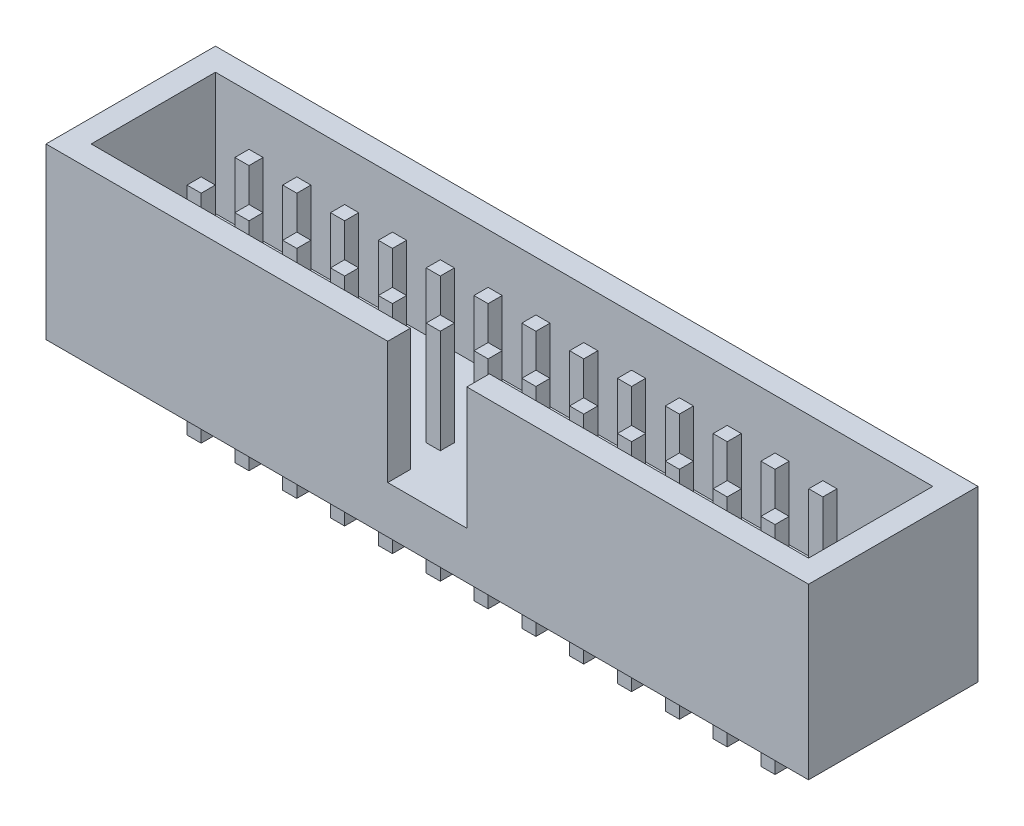
SolidWorks part; units mm, degrees
ref_plane "前视基准面" through (0, 0, 0) normal (0, 0, 1) x (1, 0, 0)
ref_plane "上视基准面" through (0, 0, 0) normal (0, 1, 0) x (1, 0, 0)
ref_plane "右视基准面" through (0, 0, 0) normal (1, 0, 0) x (0, 0, -1)
sketch "草图1" plane through (0, 0, 0) normal (0, 1, 0) x (1, 0, 0)
  line L0 (0, 85.0964) -> (0, -118.2031) construction
  line L1 (-20.25, 4.5) -> (20.25, 4.5)
  line L2 (-20.25, 4.5) -> (-20.25, -4.5)
  line L3 (-20.25, -4.5) -> (20.25, -4.5)
  line L4 (20.25, 4.5) -> (20.25, -4.5)
  line L5 (-200.5452, 0) -> (261.2352, 0) construction
  dimension "D1" = 9
  dimension "D2" = 40.5
extrude "拉伸1" add sketch "草图1" along normal blind 9
sketch "草图2" plane through (0, 9, 0) normal (0, 1, 0) x (-1, 0, 0)
  line L8 (-19.05, 3.3) -> (-19.05, -3.3)
  line L9 (19.05, 3.3) -> (-19.05, 3.3)
  line L10 (19.05, -3.3) -> (19.05, 3.3)
  line L11 (-19.05, -3.3) -> (19.05, -3.3)
  line L12 (-19.05, 3.3) -> (-19.05, -3.3)
  line L13 (19.05, 3.3) -> (-19.05, 3.3)
  line L14 (19.05, -3.3) -> (19.05, 3.3)
  line L15 (-19.05, -3.3) -> (19.05, -3.3)
  dimension "D1" = 1.2
extrude "切除-拉伸1" cut sketch "草图2" against normal blind 6.5
sketch "草图3" plane through (0, 0, 4.5) normal (0, 0, 1) x (1, 0, 0)
  line L0 (-20.25, 9) -> (20.25, 9) construction
  line L1 (-2.1, 9) -> (2.1, 9)
  line L2 (-2.1, 9) -> (-2.1, 2.5)
  line L3 (-2.1, 2.5) -> (2.1, 2.5)
  line L4 (2.1, 9) -> (2.1, 2.5)
  line L5 (-19.05, 2.5) -> (19.05, 2.5) construction
  line L6 (0, 9.4226) -> (0, -4.0288) construction
  dimension "D1" = 4.2
extrude "切除-拉伸2" cut sketch "草图3" against normal blind 6.5
sketch "草图5" plane through (0, 0, 0) normal (0, -1, 0) x (1, 0, 0)
  line L0 (0, 6.0683) -> (0, -6.9786) construction
  line L1 (-21.1981, 0) -> (21.4095, 0) construction
  line L2 (-2.4898, 1.27) -> (1.0953, 1.27) construction
  line L3 (-0.375, 0.895) -> (0.375, 0.895)
  line L4 (-0.375, 0.895) -> (-0.375, 1.645)
  line L5 (-0.375, 1.645) -> (0.375, 1.645)
  line L6 (0.375, 0.895) -> (0.375, 1.645)
  line L7 (2.165, 0.895) -> (2.915, 0.895)
  line L8 (2.165, 0.895) -> (2.165, 1.645)
  line L9 (2.165, 1.645) -> (2.915, 1.645)
  line L10 (2.915, 0.895) -> (2.915, 1.645)
  line L11 (4.705, 0.895) -> (5.455, 0.895)
  line L12 (4.705, 0.895) -> (4.705, 1.645)
  line L13 (4.705, 1.645) -> (5.455, 1.645)
  line L14 (5.455, 0.895) -> (5.455, 1.645)
  line L15 (7.245, 0.895) -> (7.995, 0.895)
  line L16 (7.245, 0.895) -> (7.245, 1.645)
  line L17 (7.245, 1.645) -> (7.995, 1.645)
  line L18 (7.995, 0.895) -> (7.995, 1.645)
  line L19 (9.785, 0.895) -> (10.535, 0.895)
  line L20 (9.785, 0.895) -> (9.785, 1.645)
  line L21 (9.785, 1.645) -> (10.535, 1.645)
  line L22 (10.535, 0.895) -> (10.535, 1.645)
  line L23 (12.325, 0.895) -> (13.075, 0.895)
  line L24 (12.325, 0.895) -> (12.325, 1.645)
  line L25 (12.325, 1.645) -> (13.075, 1.645)
  line L26 (13.075, 0.895) -> (13.075, 1.645)
  line L27 (14.865, 0.895) -> (15.615, 0.895)
  line L28 (14.865, 0.895) -> (14.865, 1.645)
  line L29 (14.865, 1.645) -> (15.615, 1.645)
  line L30 (15.615, 0.895) -> (15.615, 1.645)
  line L31 (-2.915, 0.895) -> (-2.165, 0.895)
  line L32 (-2.915, 0.895) -> (-2.915, 1.645)
  line L33 (-2.915, 1.645) -> (-2.165, 1.645)
  line L34 (-2.165, 0.895) -> (-2.165, 1.645)
  line L35 (-5.455, 0.895) -> (-4.705, 0.895)
  line L36 (-5.455, 0.895) -> (-5.455, 1.645)
  line L37 (-5.455, 1.645) -> (-4.705, 1.645)
  line L38 (-4.705, 0.895) -> (-4.705, 1.645)
  line L39 (-7.995, 0.895) -> (-7.245, 0.895)
  line L40 (-7.995, 0.895) -> (-7.995, 1.645)
  line L41 (-7.995, 1.645) -> (-7.245, 1.645)
  line L42 (-7.245, 0.895) -> (-7.245, 1.645)
  line L43 (-10.535, 0.895) -> (-9.785, 0.895)
  line L44 (-10.535, 0.895) -> (-10.535, 1.645)
  line L45 (-10.535, 1.645) -> (-9.785, 1.645)
  line L46 (-9.785, 0.895) -> (-9.785, 1.645)
  line L47 (-13.075, 0.895) -> (-12.325, 0.895)
  line L48 (-13.075, 0.895) -> (-13.075, 1.645)
  line L49 (-13.075, 1.645) -> (-12.325, 1.645)
  line L50 (-12.325, 0.895) -> (-12.325, 1.645)
  line L51 (-15.615, 0.895) -> (-14.865, 0.895)
  line L52 (-15.615, 0.895) -> (-15.615, 1.645)
  line L53 (-15.615, 1.645) -> (-14.865, 1.645)
  line L54 (-14.865, 0.895) -> (-14.865, 1.645)
  line L55 (-2.4898, -1.27) -> (1.0953, -1.27) construction
  line L56 (-14.865, -0.895) -> (-14.865, -1.645)
  line L57 (-15.615, -1.645) -> (-14.865, -1.645)
  line L58 (-15.615, -0.895) -> (-15.615, -1.645)
  line L59 (-15.615, -0.895) -> (-14.865, -0.895)
  line L60 (-12.325, -0.895) -> (-12.325, -1.645)
  line L61 (-13.075, -1.645) -> (-12.325, -1.645)
  line L62 (-13.075, -0.895) -> (-13.075, -1.645)
  line L63 (-13.075, -0.895) -> (-12.325, -0.895)
  line L64 (-9.785, -0.895) -> (-9.785, -1.645)
  line L65 (-10.535, -1.645) -> (-9.785, -1.645)
  line L66 (-10.535, -0.895) -> (-10.535, -1.645)
  line L67 (-10.535, -0.895) -> (-9.785, -0.895)
  line L68 (-7.245, -0.895) -> (-7.245, -1.645)
  line L69 (-7.995, -1.645) -> (-7.245, -1.645)
  line L70 (-7.995, -0.895) -> (-7.995, -1.645)
  line L71 (-7.995, -0.895) -> (-7.245, -0.895)
  line L72 (-4.705, -0.895) -> (-4.705, -1.645)
  line L73 (-5.455, -1.645) -> (-4.705, -1.645)
  line L74 (-5.455, -0.895) -> (-5.455, -1.645)
  line L75 (-5.455, -0.895) -> (-4.705, -0.895)
  line L76 (-2.165, -0.895) -> (-2.165, -1.645)
  line L77 (-2.915, -1.645) -> (-2.165, -1.645)
  line L78 (-2.915, -0.895) -> (-2.915, -1.645)
  line L79 (-2.915, -0.895) -> (-2.165, -0.895)
  line L80 (15.615, -0.895) -> (15.615, -1.645)
  line L81 (14.865, -1.645) -> (15.615, -1.645)
  line L82 (14.865, -0.895) -> (14.865, -1.645)
  line L83 (14.865, -0.895) -> (15.615, -0.895)
  line L84 (13.075, -0.895) -> (13.075, -1.645)
  line L85 (12.325, -1.645) -> (13.075, -1.645)
  line L86 (12.325, -0.895) -> (12.325, -1.645)
  line L87 (12.325, -0.895) -> (13.075, -0.895)
  line L88 (10.535, -0.895) -> (10.535, -1.645)
  line L89 (9.785, -1.645) -> (10.535, -1.645)
  line L90 (9.785, -0.895) -> (9.785, -1.645)
  line L91 (9.785, -0.895) -> (10.535, -0.895)
  line L92 (7.995, -0.895) -> (7.995, -1.645)
  line L93 (7.245, -1.645) -> (7.995, -1.645)
  line L94 (7.245, -0.895) -> (7.245, -1.645)
  line L95 (7.245, -0.895) -> (7.995, -0.895)
  line L96 (5.455, -0.895) -> (5.455, -1.645)
  line L97 (4.705, -1.645) -> (5.455, -1.645)
  line L98 (4.705, -0.895) -> (4.705, -1.645)
  line L99 (4.705, -0.895) -> (5.455, -0.895)
  line L100 (2.915, -0.895) -> (2.915, -1.645)
  line L101 (2.165, -1.645) -> (2.915, -1.645)
  line L102 (2.165, -0.895) -> (2.165, -1.645)
  line L103 (2.165, -0.895) -> (2.915, -0.895)
  line L104 (0.375, -0.895) -> (0.375, -1.645)
  line L105 (-0.375, -1.645) -> (0.375, -1.645)
  line L106 (-0.375, -0.895) -> (-0.375, -1.645)
  line L107 (-0.375, -0.895) -> (0.375, -0.895)
  dimension "D1" = 0.75
  dimension "D2" = 0.75
  dimension "D3" = 1.27
extrude "拉伸2" add sketch "草图5" along normal blind 3.5 and the other way offset from surface 1 other way up to face at (0, 9, 1.3)
